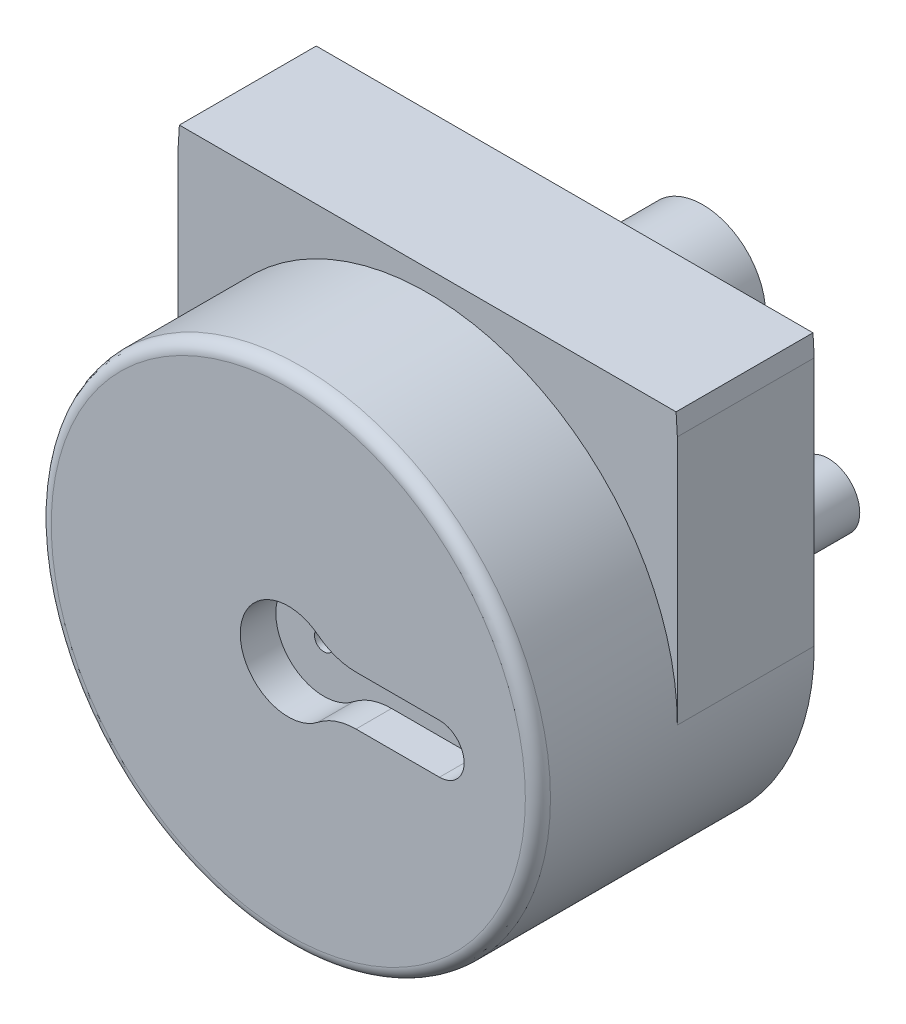
SolidWorks part; units mm, degrees
ref_plane "Front Plane" through (0, 0, 0) normal (0, 0, 1) x (1, 0, 0)
ref_plane "Top Plane" through (0, 0, 0) normal (0, 1, 0) x (1, 0, 0)
ref_plane "Right Plane" through (0, 0, 0) normal (1, 0, 0) x (0, 0, -1)
sketch "Sketch2" plane through (0, 0, 0) normal (0, 0, 1) x (1, 0, 0)
  circle A0 centre (0, 0) radius 39.75
  dimension "D1" = 79.5
extrude "Boss-Extrude1" add sketch "Sketch2" along normal blind 44
sketch "Sketch3" plane through (0, 0, 0) normal (0, 1, 0) x (1, 0, 0)
  line L0 (39.75, -44) -> (39.75, 0) construction
  line L1 (-39.75, 0) -> (39.75, 0)
  line L2 (-39.75, 0) -> (-39.75, -21.8)
  line L3 (-39.75, -21.8) -> (39.75, -21.8)
  line L4 (39.75, 0) -> (39.75, -21.8)
  dimension "D1" = 21.8
extrude "Boss-Extrude2" add sketch "Sketch3" along normal through all
sketch "Sketch4" plane through (0, 0, 0) normal (0, 0, -1) x (-1, 0, 0)
  line L0 (0, 0) -> (0, 203.2) construction
  line L1 (-39.75, 39.75) -> (-29.9473, 204.9767)
  line L2 (39.75, 39.75) -> (29.9473, 204.9767)
  line L3 (-39.75, 39.75) -> (39.75, 39.75)
  circle A0 centre (0, 203.2) radius 30
  circle A1 centre (0, 203.2) radius 25.9
  line M5 (39.75, 39.75) -> (-39.75, 39.75)
  dimension "D2" = 60
  dimension "D3" = 51.8
  dimension "D1" = 203.2
extrude "Boss-Extrude3" add sketch "Sketch4" against normal up to surface (21.8 mm away) contours L0 L2 A0 M5 | L3 L0 A0 L1 | A0 region at (18.2462, 107.3979, 0) region at (-18.2462, 107.3979, 0) region at (21.2148, 183.2065, 0) up to face at (29.2442, 29.2442, 21.8)
sketch "Sketch5" plane through (0, 0, 0) normal (0, 0, -1) x (-1, 0, 0)
  line L0 (-20, 0) -> (20, 0) construction
  line L1 (0, 20) -> (0, -20) construction
  line L2 (0, 0) -> (0, 177.3) construction
  circle A0 centre (-20, 0) radius 5
  circle A1 centre (0, -20) radius 10
  circle A2 centre (0, 20) radius 10
  circle A3 centre (20, 0) radius 5
  circle A4 centre (0, 203.2) radius 25.9 construction
  circle A5 centre (0, 147.3) radius 5
  circle A6 centre (0, 117.3) radius 10
  circle A7 centre (0, -20) radius 5.125
  circle A8 centre (0, 20) radius 5.125
  circle A9 centre (0, 117.3) radius 5.125
  point P5 (0, 0)
  point P9 (0, 0)
  dimension "D3" = 10
  dimension "D4" = 20
  dimension "D7" = 10
  dimension "D8" = 10
  dimension "D9" = 20
  dimension "D10" = 20
  dimension "D11" = 10.25
  dimension "D12" = 10.25
  dimension "D13" = 10.25
  dimension "D1" = 40
  dimension "D2" = 40
  dimension "D5" = 30
  dimension "D6" = 30
extrude "Boss-Extrude4" add sketch "Sketch5" along normal blind 22
extrude "Boss-Extrude5" add sketch "Sketch4<3>" along normal blind 10 from surface contours A1 region at (0, 203.2, 0) starting at face at (0, 92.9045, 21.8)
sketch "Sketch4<3>" plane through (0, 0, 0) normal (0, 0, -1) x (-1, 0, 0) same geometry as "Sketch4"
sketch "Sketch6" plane through (0, 0, 44) normal (0, 0, 1) x (1, 0, 0)
  line L0 (24.0717, 0) -> (20.0717, 0) construction
  line L1 (10.7762, 3.725) -> (24.0717, 3.725)
  line L2 (24.0717, -3) -> (20.0717, -3)
  line L7 (10.7762, -3.725) -> (24.0717, -3.725)
  line L8 (24.0717, 3) -> (20.0717, 3)
  line L9 (10.7762, -3.925) -> (24.0717, -3.925)
  line L10 (10.7762, 3.925) -> (24.0717, 3.925)
  arc A2 (24.0717, -3.725) -> (24.0717, 3.725) centre (24.0717, 0) ccw
  arc A3 (24.0717, -3) -> (24.0717, 3) centre (24.0717, 0) ccw
  arc A4 (6.4519, 3.725) -> (7.4142, 0.729) centre (0, 0) cw
  arc A5 (4.6007, -5.8597) -> (10.7762, -3.725) centre (10.7762, -13.725) cw
  arc A6 (4.6007, 5.8597) -> (10.7762, 3.725) centre (10.7762, 13.725) ccw
  arc A7 (4.7242, 6.017) -> (4.7242, -6.017) centre (0, 0) ccw
  arc A8 (4.7242, -6.017) -> (10.7762, -3.925) centre (10.7762, -13.725) cw
  arc A9 (24.0717, -3.925) -> (24.0717, 3.925) centre (24.0717, 0) ccw
  arc A10 (4.7242, 6.017) -> (10.7762, 3.925) centre (10.7762, 13.725) ccw
  circle A11 centre (0, 0) radius 1.5
  circle A12 centre (8.95, 0) radius 1.7
  circle A13 centre (20.0717, 0) radius 1.5
  circle A14 centre (24.0717, 0) radius 1.5
  arc A15 (7.4142, -0.729) -> (6.4519, -3.725) centre (0, 0) cw
  point P1 (22.0717, 0)
  point P4 (0, 0)
  point P5 (0, 0)
  point P8 (0, 0)
  point P10 (-27.75, 0)
  point P13 (27.75, 0)
  dimension "D4" = 10
  dimension "D1" = 7.45
  dimension "D5" = 3
  dimension "D6" = 3
  dimension "D7" = 3
  dimension "D2" = 24.0717
  dimension "D3" = 6
extrude "Cut-Extrude1(NEW)" cut sketch "Sketch6" against normal blind 5.67 contours A10 A7 A8 L9 A9 L10 A14 A13 A11 A12 region at (7.4478, -4.0961, 44)
fillet "Fillet1" radius 2 1 edges at (39.75, 0, 44)
sketch "Sketch7" plane through (41.9606, 2.4895, 0) normal (0.9982, 0.0592, 0) x (0, 0, -1)
  line L0 (-1.8, 184.6917) -> (-1.8, 181.1738)
  line L1 (-11.8422, 116.1491) -> (-16.6583, 116.1491)
  line L2 (-2, 184.4917) -> (-2, 181.1738)
  line L3 (-15.0457, 174.0211) -> (-19.8, 174.0211)
  line L4 (-19.8, 174.0211) -> (-19.8, 178.4187)
  line L5 (-19.8, 178.4187) -> (-13.7794, 178.4187)
  line L6 (-11.6329, 179.8846) -> (-19.8, 179.8846)
  line L7 (-19.8, 179.8846) -> (-19.8, 184.4917)
  line L8 (-19.8, 184.4917) -> (-2, 184.4917)
  line L9 (-4.9318, 179.8846) -> (-8.9106, 179.8846)
  line L10 (-7.2975, 178.4187) -> (-6.3126, 178.4187)
  line L11 (-2, 162.5453) -> (-2, 154.5877)
  line L12 (-2, 154.5877) -> (-5.56, 154.5877)
  line L13 (-5.56, 154.5877) -> (-5.56, 157.9383)
  line L14 (-5.56, 157.9383) -> (-8.9106, 157.9383)
  line L15 (-8.9106, 157.9383) -> (-8.9106, 154.7971)
  line L16 (-8.9106, 154.7971) -> (-12.2612, 154.7971)
  line L17 (-12.2612, 154.7971) -> (-12.2612, 157.9383)
  line L18 (-12.2612, 157.9383) -> (-16.24, 157.9383)
  line L19 (-16.24, 157.9383) -> (-16.24, 154.3783)
  line L20 (-16.24, 154.3783) -> (-19.8, 154.3783)
  line L21 (-19.8, 154.3783) -> (-19.8, 162.5453)
  line L22 (-19.8, 162.5453) -> (-2, 162.5453)
  line L23 (-2, 143.3213) -> (-2, 139.8038)
  line L24 (-8.2791, 132.4319) -> (-14.5124, 132.4319)
  line L25 (-19.8, 137.3923) -> (-19.8, 143.3213)
  line L26 (-19.8, 143.3213) -> (-2, 143.3213)
  line L27 (-4.9318, 138.7143) -> (-16.8682, 138.7143)
  line L28 (-14.2342, 137.039) -> (-7.1829, 137.039)
  line L29 (-2, 120.9561) -> (-2, 116.2346)
  line L30 (-13.8939, 110.0667) -> (-15.566, 110.0667)
  line L31 (-19.8, 115.5441) -> (-19.8, 120.9561)
  line L32 (-19.8, 120.9561) -> (-2, 120.9561)
  line L33 (-4.9318, 116.3491) -> (-8.9106, 116.3491)
  line L34 (-11.6329, 116.3491) -> (-16.8682, 116.3491)
  line L35 (-15.1242, 114.6738) -> (-13.3769, 114.6738)
  line L36 (-2, 93.9839) -> (-19.8, 93.9839)
  line L37 (-19.8, 93.9839) -> (-19.8, 98.591)
  line L38 (-19.8, 98.591) -> (-2, 98.591)
  line L39 (-2, 98.591) -> (-2, 93.9839)
  line L40 (-2, 82.2987) -> (-2, 78.9809)
  line L41 (-15.0457, 71.8281) -> (-19.8, 71.8281)
  line L42 (-19.8, 71.8281) -> (-19.8, 76.2258)
  line L43 (-19.8, 76.2258) -> (-13.7794, 76.2258)
  line L44 (-11.6329, 77.6917) -> (-19.8, 77.6917)
  line L45 (-19.8, 77.6917) -> (-19.8, 82.2987)
  line L46 (-19.8, 82.2987) -> (-2, 82.2987)
  line L47 (-4.9318, 77.6917) -> (-8.9106, 77.6917)
  line L48 (-7.2975, 76.2258) -> (-6.3126, 76.2258)
  line L49 (-2, 60.3524) -> (-2, 56.8349)
  line L50 (-8.2791, 49.463) -> (-14.5124, 49.463)
  line L51 (-19.8, 54.4234) -> (-19.8, 60.3524)
  line L52 (-19.8, 60.3524) -> (-2, 60.3524)
  line L53 (-4.9318, 55.7453) -> (-16.8682, 55.7453)
  line L54 (-14.2342, 54.07) -> (-7.1829, 54.07)
  line L55 (-15.0442, 173.8211) -> (-20, 173.8211)
  line L56 (-20, 173.8211) -> (-20, 178.6187)
  line L57 (-20, 178.6187) -> (-13.7794, 178.6187)
  line L58 (-11.8379, 179.6846) -> (-20, 179.6846)
  line L59 (-20, 179.6846) -> (-20, 184.6917)
  line L60 (-20, 184.6917) -> (-1.8, 184.6917)
  line L61 (-7.2947, 178.6187) -> (-6.3136, 178.6187)
  line L62 (-5.1372, 179.6846) -> (-8.7079, 179.6846)
  line L63 (-20, 162.7453) -> (-1.8, 162.7453)
  line L64 (-1.8, 162.7453) -> (-1.8, 154.3877)
  line L65 (-1.8, 154.3877) -> (-5.76, 154.3877)
  line L66 (-5.76, 154.3877) -> (-5.76, 157.7383)
  line L67 (-5.76, 157.7383) -> (-8.7106, 157.7383)
  line L68 (-8.7106, 157.7383) -> (-8.7106, 154.5971)
  line L69 (-8.7106, 154.5971) -> (-12.4612, 154.5971)
  line L70 (-12.4612, 154.5971) -> (-12.4612, 157.7383)
  line L71 (-12.4612, 157.7383) -> (-16.04, 157.7383)
  line L72 (-16.04, 157.7383) -> (-16.04, 154.1783)
  line L73 (-16.04, 154.1783) -> (-20, 154.1783)
  line L74 (-20, 154.1783) -> (-20, 162.7453)
  line L75 (-20, 143.5213) -> (-1.8, 143.5213)
  line L76 (-1.8, 143.5213) -> (-1.8, 139.8038)
  line L77 (-8.2784, 132.2319) -> (-14.5128, 132.2319)
  line L78 (-20, 137.3909) -> (-20, 143.5213)
  line L79 (-15.1267, 114.8738) -> (-13.3758, 114.8738)
  line L80 (-5.1361, 116.1491) -> (-8.7058, 116.1491)
  line L81 (-20, 98.791) -> (-1.8, 98.791)
  line L82 (-1.8, 98.791) -> (-1.8, 93.7839)
  line L83 (-5.1349, 138.5143) -> (-16.6645, 138.5143)
  line L84 (-14.2351, 137.239) -> (-7.1805, 137.239)
  line L85 (-20, 121.1561) -> (-1.8, 121.1561)
  line L86 (-1.8, 121.1561) -> (-1.8, 116.2334)
  line L87 (-13.8936, 109.8667) -> (-15.566, 109.8667)
  line L88 (-20, 115.5431) -> (-20, 121.1561)
  line L89 (-1.8, 93.7839) -> (-20, 93.7839)
  line L90 (-20, 93.7839) -> (-20, 98.791)
  line L91 (-20, 82.4987) -> (-1.8, 82.4987)
  line L92 (-1.8, 82.4987) -> (-1.8, 78.9809)
  line L93 (-15.0442, 71.6281) -> (-20, 71.6281)
  line L94 (-20, 71.6281) -> (-20, 76.4258)
  line L95 (-20, 76.4258) -> (-13.7794, 76.4258)
  line L96 (-11.8379, 77.4917) -> (-20, 77.4917)
  line L97 (-20, 77.4917) -> (-20, 82.4987)
  line L98 (-7.2947, 76.4258) -> (-6.3136, 76.4258)
  line L99 (-5.1372, 77.4917) -> (-8.7079, 77.4917)
  line L100 (-14.2351, 54.27) -> (-7.1805, 54.27)
  line L101 (-5.1349, 55.5453) -> (-16.6645, 55.5453)
  line L102 (-20, 54.4219) -> (-20, 60.5524)
  line L103 (-20, 60.5524) -> (-1.8, 60.5524)
  line L104 (-1.8, 60.5524) -> (-1.8, 56.8349)
  line L105 (-8.2784, 49.263) -> (-14.5128, 49.263)
  spline S0 degree 3 poles (-2, 181.1738) (-1.9981, 180.6655) (-2.0068, 179.9357) (-2.034, 179.0075) (-2.0583, 178.4118) (-2.0946, 177.8838) (-2.1365, 177.4223) (-2.1832, 177.0267) (-2.2422, 176.6885) (-2.3184, 176.3914) (-2.4187, 176.1172) (-2.5379, 175.8548) (-2.6869, 175.6074) (-2.8617, 175.3763) (-3.0552, 175.1541) (-3.2763, 174.948) (-3.5217, 174.7536) (-3.7998, 174.5772) (-4.1159, 174.4286) (-4.4681, 174.2996) (-4.8602, 174.2012) (-5.2883, 174.1194) (-5.9348, 174.0377) (-6.4412, 174.0257) (-6.7903, 174.0211) knots 0 0 0 0 0.148543 0.213274 0.27134 0.322776 0.367908 0.406771 0.439156 0.468147 0.496277 0.524371 0.552249 0.580489 0.608944 0.638258 0.668673 0.700331 0.734261 0.77056 0.809755 0.852263 0.897886 1 1 1 1
  spline S1 degree 3 poles (-6.7903, 174.0211) (-7.1039, 174.0159) (-7.5537, 174.0372) (-8.1248, 174.0861) (-8.4902, 174.1472) (-8.8148, 174.2161) (-9.0987, 174.3045) (-9.3418, 174.4065) (-9.5475, 174.5307) (-9.7181, 174.6841) (-9.8698, 174.8618) (-10.0023, 175.0725) (-10.1145, 175.3152) (-10.2133, 175.5875) (-10.3205, 176.0108) (-10.3706, 176.3476) (-10.3896, 176.5831) knots 0 0 0 0 0.183754 0.264085 0.33602 0.400896 0.458558 0.510133 0.555226 0.598736 0.644114 0.691853 0.744219 0.800677 0.861499 1 1 1 1
  spline S2 degree 3 poles (-10.3896, 176.5831) (-10.4477, 176.3705) (-10.53, 176.0622) (-10.6742, 175.6791) (-10.7897, 175.4345) (-10.9067, 175.215) (-11.0338, 175.0254) (-11.1684, 174.8627) (-11.3529, 174.6892) (-11.5852, 174.5151) (-11.8564, 174.3409) (-12.1197, 174.2167) (-12.3412, 174.1385) (-12.543, 174.1055) (-12.7439, 174.0834) (-12.9983, 174.0648) (-13.3059, 174.0488) (-13.6659, 174.0363) (-14.2516, 174.0213) (-14.7174, 174.0259) (-15.0457, 174.0211) knots 0 0 0 0 0.110219 0.159211 0.20432 0.245296 0.283389 0.318211 0.350594 0.409678 0.463061 0.511332 0.554938 0.579849 0.613314 0.655951 0.707257 0.767249 0.835943 1 1 1 1
  spline S3 degree 3 poles (-13.7794, 178.4187) (-13.5603, 178.4206) (-13.2487, 178.4204) (-12.8563, 178.4494) (-12.6138, 178.474) (-12.4051, 178.5065) (-12.2319, 178.5444) (-12.0913, 178.5887) (-11.9798, 178.6452) (-11.8926, 178.722) (-11.8245, 178.8214) (-11.7614, 178.9389) (-11.7129, 179.0826) (-11.6789, 179.2498) (-11.6423, 179.519) (-11.6342, 179.7339) (-11.6329, 179.8846) knots 0 0 0 0 0.208642 0.296034 0.374307 0.440504 0.496897 0.54284 0.580443 0.615002 0.652158 0.694401 0.741661 0.795804 0.856563 1 1 1 1
  spline S4 degree 3 poles (-8.9106, 179.8846) (-8.9127, 179.6528) (-8.8925, 179.3307) (-8.8017, 178.9494) (-8.7231, 178.769) (-8.6251, 178.6601) (-8.5222, 178.5947) (-8.3901, 178.5409) (-8.2286, 178.4959) (-8.038, 178.4611) (-7.7252, 178.4234) (-7.474, 178.4237) (-7.2975, 178.4187) knots 0 0 0 0 0.263059 0.362536 0.443753 0.482229 0.526771 0.580464 0.643421 0.71635 0.799709 1 1 1 1
  spline S5 degree 3 poles (-6.3126, 178.4187) (-6.0777, 178.4211) (-5.7485, 178.4373) (-5.374, 178.5775) (-5.1844, 178.7238) (-5.0685, 178.9346) (-4.9447, 179.3168) (-4.9363, 179.6497) (-4.9318, 179.8846) knots 0 0 0 0 0.296724 0.405999 0.497474 0.590179 0.702697 1 1 1 1
  spline S6 degree 3 poles (-2, 139.8038) (-1.9956, 139.2824) (-2.0094, 138.534) (-2.0395, 137.583) (-2.0704, 136.9718) (-2.117, 136.4308) (-2.1678, 135.957) (-2.2277, 135.5525) (-2.3206, 135.1143) (-2.4728, 134.6455) (-2.6938, 134.1448) (-2.9758, 133.7187) (-3.306, 133.3657) (-3.6705, 133.0823) (-4.0556, 132.8554) (-4.4605, 132.687) (-4.8224, 132.5944) (-5.145, 132.5497) (-5.4395, 132.5163) (-5.7856, 132.4926) (-6.1836, 132.4682) (-6.6332, 132.4541) (-7.3377, 132.4339) (-7.8919, 132.4347) (-8.2791, 132.4319) knots 0 0 0 0 0.131289 0.188445 0.2396 0.285351 0.325141 0.359593 0.388249 0.437842 0.483436 0.525634 0.565855 0.604586 0.641514 0.678082 0.71465 0.735196 0.760065 0.789259 0.822545 0.860469 0.902502 1 1 1 1
  spline S7 degree 3 poles (-14.5124, 132.4319) (-14.8788, 132.4334) (-15.4037, 132.4345) (-16.0701, 132.4621) (-16.4954, 132.4892) (-16.8711, 132.5159) (-17.1978, 132.5544) (-17.4737, 132.6035) (-17.7737, 132.6699) (-18.0937, 132.7877) (-18.4383, 132.9635) (-18.7347, 133.1895) (-18.9908, 133.4536) (-19.2002, 133.7606) (-19.376, 134.0986) (-19.5222, 134.4686) (-19.6098, 134.8037) (-19.666, 135.0966) (-19.7004, 135.3469) (-19.7347, 135.6226) (-19.7552, 135.9263) (-19.7747, 136.2546) (-19.7999, 136.7463) (-19.7961, 137.1285) (-19.8, 137.3923) knots 0 0 0 0 0.124488 0.178251 0.226503 0.269237 0.306181 0.338157 0.364398 0.41045 0.453534 0.495323 0.536458 0.577977 0.621061 0.66564 0.712819 0.738467 0.766915 0.798622 0.832803 0.870286 0.91034 1 1 1 1
  spline S8 degree 3 poles (-16.8682, 138.7143) (-16.8674, 138.5419) (-16.8597, 138.2945) (-16.8125, 137.9868) (-16.774, 137.7943) (-16.7118, 137.6326) (-16.647, 137.4922) (-16.5606, 137.3829) (-16.4579, 137.2963) (-16.325, 137.2337) (-16.1549, 137.1834) (-15.9413, 137.1388) (-15.6846, 137.1004) (-15.3843, 137.0715) (-14.8966, 137.0461) (-14.5081, 137.0366) (-14.2342, 137.039) knots 0 0 0 0 0.137111 0.195798 0.247293 0.292517 0.333199 0.369595 0.402207 0.439014 0.485321 0.542924 0.61215 0.691372 0.782487 1 1 1 1
  spline S9 degree 3 poles (-7.1829, 137.039) (-6.9964, 137.0344) (-6.7303, 137.0433) (-6.3932, 137.051) (-6.1815, 137.06) (-5.9985, 137.0747) (-5.8429, 137.0846) (-5.7157, 137.1062) (-5.582, 137.1289) (-5.443, 137.1804) (-5.2977, 137.2649) (-5.1805, 137.3845) (-5.0837, 137.5372) (-5.0121, 137.741) (-4.9386, 138.1366) (-4.9349, 138.4712) (-4.9318, 138.7143) knots 0 0 0 0 0.161879 0.231001 0.29259 0.34573 0.390378 0.427726 0.457613 0.507913 0.555475 0.602325 0.65169 0.711291 0.788512 1 1 1 1
  spline S10 degree 3 poles (-2, 116.2346) (-2.004, 115.8844) (-2.0071, 115.3757) (-2.042, 114.7201) (-2.0831, 114.2796) (-2.1261, 113.872) (-2.1857, 113.4989) (-2.2533, 113.1591) (-2.3315, 112.8491) (-2.428, 112.5637) (-2.5413, 112.2943) (-2.6802, 112.0405) (-2.8415, 111.8018) (-3.0217, 111.574) (-3.2259, 111.3622) (-3.4483, 111.1608) (-3.6966, 110.9765) (-3.9726, 110.805) (-4.2921, 110.6683) (-4.6448, 110.5411) (-5.0405, 110.4471) (-5.4714, 110.3665) (-6.1256, 110.2999) (-6.6357, 110.27) (-6.9899, 110.2761) knots 0 0 0 0 0.114386 0.166124 0.214411 0.258869 0.299987 0.337788 0.372007 0.404341 0.436105 0.467354 0.498678 0.530114 0.562118 0.594663 0.628011 0.663022 0.700498 0.741288 0.785356 0.833155 0.88442 1 1 1 1
  spline S11 degree 3 poles (-6.9899, 110.2761) (-7.227, 110.2723) (-7.5686, 110.2901) (-8.0022, 110.3443) (-8.2864, 110.3943) (-8.5399, 110.4664) (-8.7663, 110.5513) (-8.964, 110.6518) (-9.1363, 110.7725) (-9.2872, 110.9181) (-9.4253, 111.0915) (-9.5554, 111.2929) (-9.6721, 111.5272) (-9.7889, 111.7874) (-9.924, 112.1979) (-10.0157, 112.5216) (-10.0624, 112.7498) knots 0 0 0 0 0.159593 0.229912 0.29415 0.353664 0.407126 0.456721 0.502563 0.548271 0.597357 0.65154 0.709345 0.77347 0.843372 1 1 1 1
  spline S12 degree 3 poles (-10.0624, 112.7498) (-10.1183, 112.5059) (-10.2185, 112.155) (-10.399, 111.7216) (-10.5418, 111.4376) (-10.7034, 111.1867) (-10.8795, 110.9669) (-11.0712, 110.7773) (-11.2803, 110.6181) (-11.5114, 110.4844) (-11.7699, 110.3755) (-12.0528, 110.2751) (-12.3685, 110.2033) (-12.7087, 110.1399) (-13.2206, 110.0833) (-13.6187, 110.0677) (-13.8939, 110.0667) knots 0 0 0 0 0.14404 0.209305 0.269928 0.326675 0.380677 0.43171 0.481413 0.531464 0.584861 0.642612 0.703952 0.770914 0.841672 1 1 1 1
  spline S13 degree 3 poles (-15.566, 110.0667) (-15.8508, 110.0669) (-16.2639, 110.0774) (-16.7938, 110.1221) (-17.1478, 110.1668) (-17.4717, 110.2267) (-17.768, 110.2926) (-18.0337, 110.3781) (-18.3432, 110.5062) (-18.6861, 110.7034) (-19.0241, 111.0158) (-19.3008, 111.3821) (-19.4658, 111.7453) (-19.5628, 112.086) (-19.6261, 112.4046) (-19.682, 112.7823) (-19.7208, 113.2195) (-19.7579, 113.7157) (-19.7943, 114.4967) (-19.7954, 115.1134) (-19.8, 115.5441) knots 0 0 0 0 0.102225 0.148189 0.190817 0.230204 0.266378 0.299678 0.330209 0.386533 0.440563 0.494267 0.550311 0.582518 0.621285 0.666789 0.719486 0.778749 0.845365 1 1 1 1
  spline S14 degree 2 poles (-8.9106, 116.3491) (-8.9038, 116.0939) (-8.9008, 115.8386) knots 0 0 0 1 1 1
  spline S15 degree 3 poles (-8.9008, 115.8386) (-8.9036, 115.6319) (-8.8787, 115.3414) (-8.7282, 115.0182) (-8.5926, 114.8871) (-8.4492, 114.824) (-8.3051, 114.7827) (-8.1215, 114.7526) (-7.9002, 114.7227) (-7.638, 114.701) (-7.2116, 114.6784) (-6.8721, 114.6739) (-6.6332, 114.6738) knots 0 0 0 0 0.207123 0.283932 0.350841 0.389257 0.439129 0.499893 0.574453 0.661745 0.761896 1 1 1 1
  spline S16 degree 3 poles (-6.6332, 114.6738) (-6.3937, 114.6721) (-6.0649, 114.6867) (-5.6703, 114.757) (-5.4631, 114.8337) (-5.3036, 114.9277) (-5.1808, 115.0341) (-5.0833, 115.1501) (-5.0215, 115.2942) (-4.9847, 115.475) (-4.9423, 115.8295) (-4.9357, 116.1287) (-4.9318, 116.3491) knots 0 0 0 0 0.247841 0.339943 0.41354 0.475302 0.530527 0.581127 0.630646 0.690893 0.771688 1 1 1 1
  spline S17 degree 3 poles (-16.8682, 116.3491) (-16.8607, 116.1854) (-16.8509, 115.9506) (-16.8087, 115.6568) (-16.7744, 115.4715) (-16.7282, 115.3109) (-16.6771, 115.1734) (-16.6194, 115.0592) (-16.5473, 114.9684) (-16.4559, 114.897) (-16.3441, 114.8341) (-16.2026, 114.7873) (-16.0376, 114.7452) (-15.846, 114.7129) (-15.5394, 114.6828) (-15.2958, 114.6696) (-15.1242, 114.6738) knots 0 0 0 0 0.168587 0.241054 0.305045 0.362185 0.41258 0.455716 0.49319 0.530665 0.574337 0.624343 0.683356 0.749349 0.823768 1 1 1 1
  spline S18 degree 3 poles (-13.3769, 114.6738) (-13.1968, 114.6716) (-12.9412, 114.6806) (-12.6194, 114.7069) (-12.4221, 114.7341) (-12.2551, 114.7745) (-12.1175, 114.8188) (-12.0065, 114.8697) (-11.9197, 114.9351) (-11.8601, 115.0258) (-11.8035, 115.1333) (-11.7595, 115.2708) (-11.721, 115.4339) (-11.689, 115.6242) (-11.6524, 115.9315) (-11.6392, 116.1765) (-11.6329, 116.3491) knots 0 0 0 0 0.182369 0.25887 0.326977 0.383772 0.432672 0.473181 0.506991 0.541018 0.58202 0.629874 0.686669 0.751678 0.825111 1 1 1 1
  spline S19 degree 3 poles (-2, 78.9809) (-1.9981, 78.4725) (-2.0068, 77.7427) (-2.034, 76.8146) (-2.0583, 76.2188) (-2.0946, 75.6909) (-2.1365, 75.2293) (-2.1832, 74.8337) (-2.2422, 74.4956) (-2.3184, 74.1985) (-2.4187, 73.9243) (-2.5379, 73.6619) (-2.6869, 73.4144) (-2.8617, 73.1834) (-3.0552, 72.9611) (-3.2763, 72.7551) (-3.5217, 72.5607) (-3.7998, 72.3842) (-4.1159, 72.2357) (-4.4681, 72.1066) (-4.8602, 72.0083) (-5.2883, 71.9265) (-5.9348, 71.8448) (-6.4412, 71.8328) (-6.7903, 71.8281) knots 0 0 0 0 0.148543 0.213274 0.27134 0.322776 0.367908 0.406771 0.439156 0.468147 0.496277 0.524371 0.552249 0.580489 0.608944 0.638258 0.668673 0.700331 0.734261 0.77056 0.809755 0.852263 0.897886 1 1 1 1
  spline S20 degree 3 poles (-6.7903, 71.8281) (-7.1039, 71.8229) (-7.5537, 71.8442) (-8.1248, 71.8931) (-8.4902, 71.9543) (-8.8148, 72.0232) (-9.0987, 72.1116) (-9.3418, 72.2136) (-9.5475, 72.3378) (-9.7181, 72.4912) (-9.8698, 72.6688) (-10.0023, 72.8796) (-10.1145, 73.1223) (-10.2133, 73.3946) (-10.3205, 73.8178) (-10.3706, 74.1547) (-10.3896, 74.3902) knots 0 0 0 0 0.183754 0.264085 0.33602 0.400896 0.458558 0.510133 0.555226 0.598736 0.644114 0.691853 0.744219 0.800677 0.861499 1 1 1 1
  spline S21 degree 3 poles (-10.3896, 74.3902) (-10.4477, 74.1775) (-10.53, 73.8692) (-10.6742, 73.4862) (-10.7897, 73.2416) (-10.9067, 73.0221) (-11.0338, 72.8325) (-11.1684, 72.6697) (-11.3529, 72.4963) (-11.5852, 72.3221) (-11.8564, 72.1479) (-12.1197, 72.0237) (-12.3412, 71.9456) (-12.543, 71.9126) (-12.7439, 71.8905) (-12.9983, 71.8719) (-13.3059, 71.8559) (-13.6659, 71.8434) (-14.2516, 71.8283) (-14.7174, 71.8329) (-15.0457, 71.8281) knots 0 0 0 0 0.110219 0.159211 0.20432 0.245296 0.283389 0.318211 0.350594 0.409678 0.463061 0.511332 0.554938 0.579849 0.613314 0.655951 0.707257 0.767249 0.835943 1 1 1 1
  spline S22 degree 3 poles (-13.7794, 76.2258) (-13.5603, 76.2277) (-13.2487, 76.2274) (-12.8563, 76.2565) (-12.6138, 76.281) (-12.4051, 76.3136) (-12.2319, 76.3515) (-12.0913, 76.3957) (-11.9798, 76.4522) (-11.8926, 76.5291) (-11.8245, 76.6284) (-11.7614, 76.746) (-11.7129, 76.8897) (-11.6789, 77.0569) (-11.6423, 77.3261) (-11.6342, 77.541) (-11.6329, 77.6917) knots 0 0 0 0 0.208642 0.296034 0.374307 0.440504 0.496897 0.54284 0.580443 0.615002 0.652158 0.694401 0.741661 0.795804 0.856563 1 1 1 1
  spline S23 degree 3 poles (-8.9106, 77.6917) (-8.9127, 77.4599) (-8.8925, 77.1377) (-8.8017, 76.7565) (-8.7231, 76.5761) (-8.6251, 76.4671) (-8.5222, 76.4017) (-8.3901, 76.3479) (-8.2286, 76.3029) (-8.038, 76.2681) (-7.7252, 76.2304) (-7.474, 76.2307) (-7.2975, 76.2258) knots 0 0 0 0 0.263059 0.362536 0.443753 0.482229 0.526771 0.580464 0.643421 0.71635 0.799709 1 1 1 1
  spline S24 degree 3 poles (-6.3126, 76.2258) (-6.0777, 76.2281) (-5.7485, 76.2444) (-5.374, 76.3846) (-5.1844, 76.5309) (-5.0685, 76.7416) (-4.9447, 77.1238) (-4.9363, 77.4568) (-4.9318, 77.6917) knots 0 0 0 0 0.296724 0.405999 0.497474 0.590179 0.702697 1 1 1 1
  spline S25 degree 3 poles (-2, 56.8349) (-1.9956, 56.3134) (-2.0094, 55.5651) (-2.0395, 54.614) (-2.0704, 54.0028) (-2.117, 53.4619) (-2.1678, 52.988) (-2.2277, 52.5836) (-2.3206, 52.1454) (-2.4728, 51.6765) (-2.6938, 51.1759) (-2.9758, 50.7498) (-3.306, 50.3968) (-3.6705, 50.1134) (-4.0556, 49.8865) (-4.4605, 49.7181) (-4.8224, 49.6255) (-5.145, 49.5808) (-5.4395, 49.5474) (-5.7856, 49.5236) (-6.1836, 49.4993) (-6.6332, 49.4852) (-7.3377, 49.4649) (-7.8919, 49.4658) (-8.2791, 49.463) knots 0 0 0 0 0.131289 0.188445 0.2396 0.285351 0.325141 0.359593 0.388249 0.437842 0.483436 0.525634 0.565855 0.604586 0.641514 0.678082 0.71465 0.735196 0.760065 0.789259 0.822545 0.860469 0.902502 1 1 1 1
  spline S26 degree 3 poles (-14.5124, 49.463) (-14.8788, 49.4645) (-15.4037, 49.4656) (-16.0701, 49.4931) (-16.4954, 49.5203) (-16.8711, 49.547) (-17.1978, 49.5855) (-17.4737, 49.6346) (-17.7737, 49.701) (-18.0937, 49.8187) (-18.4383, 49.9945) (-18.7347, 50.2205) (-18.9908, 50.4847) (-19.2002, 50.7917) (-19.376, 51.1296) (-19.5222, 51.4997) (-19.6098, 51.8348) (-19.666, 52.1277) (-19.7004, 52.378) (-19.7347, 52.6537) (-19.7552, 52.9574) (-19.7747, 53.2857) (-19.7999, 53.7774) (-19.7961, 54.1595) (-19.8, 54.4234) knots 0 0 0 0 0.124488 0.178251 0.226503 0.269237 0.306181 0.338157 0.364398 0.41045 0.453534 0.495323 0.536458 0.577977 0.621061 0.66564 0.712819 0.738467 0.766915 0.798622 0.832803 0.870286 0.91034 1 1 1 1
  spline S27 degree 3 poles (-16.8682, 55.7453) (-16.8674, 55.573) (-16.8597, 55.3256) (-16.8125, 55.0179) (-16.774, 54.8254) (-16.7118, 54.6636) (-16.647, 54.5232) (-16.5606, 54.4139) (-16.4579, 54.3274) (-16.325, 54.2647) (-16.1549, 54.2144) (-15.9413, 54.1699) (-15.6846, 54.1315) (-15.3843, 54.1025) (-14.8966, 54.0772) (-14.5081, 54.0677) (-14.2342, 54.07) knots 0 0 0 0 0.137111 0.195798 0.247293 0.292517 0.333199 0.369595 0.402207 0.439014 0.485321 0.542924 0.61215 0.691372 0.782487 1 1 1 1
  spline S28 degree 3 poles (-7.1829, 54.07) (-6.9964, 54.0655) (-6.7303, 54.0744) (-6.3932, 54.0821) (-6.1815, 54.0911) (-5.9985, 54.1058) (-5.8429, 54.1156) (-5.7157, 54.1373) (-5.582, 54.1599) (-5.443, 54.2115) (-5.2977, 54.296) (-5.1805, 54.4156) (-5.0837, 54.5683) (-5.0121, 54.7721) (-4.9386, 55.1676) (-4.9349, 55.5022) (-4.9318, 55.7453) knots 0 0 0 0 0.161879 0.231001 0.29259 0.34573 0.390378 0.427726 0.457613 0.507913 0.555475 0.602325 0.65169 0.711291 0.788512 1 1 1 1
  spline S29 degree 1 poles (-1.8, 181.1738) (-6.7873, 173.8211) knots 0 0 1 1 construction
  spline S30 degree 1 poles (-6.7873, 173.8211) (-10.4498, 175.7107) knots 0 0 1 1 construction
  spline S31 degree 1 poles (-10.4498, 175.7107) (-15.0442, 173.8211) knots 0 0 1 1 construction
  spline S32 degree 1 poles (-13.7794, 178.6187) (-11.8379, 179.6846) knots 0 0 1 1 construction
  spline S33 degree 3 poles (-1.8, 181.1738) (-1.7968, 180.3152) (-1.8179, 179.0237) (-1.9251, 177.3173) (-2.1534, 175.9722) (-2.9767, 174.8255) (-4.1703, 174.1131) (-5.4878, 173.8607) (-6.3523, 173.8269) (-6.7873, 173.8211) knots 0.000072 0.000072 0.000072 0.000072 0.250046 0.375033 0.50002 0.625007 0.749994 0.874981 0.999968 0.999968 0.999968 0.999968
  spline S34 degree 3 poles (-6.7873, 173.8211) (-7.1505, 173.8151) (-7.8758, 173.846) (-8.7843, 173.9782) (-9.5172, 174.2381) (-9.9972, 174.6501) (-10.2858, 175.1709) (-10.4037, 175.5272) (-10.4498, 175.7107) knots 0.000063 0.000063 0.000063 0.000063 0.209226 0.418389 0.52297 0.627551 0.732133 0.836714 0.836714 0.836714 0.836714
  spline S35 degree 3 poles (-10.4498, 175.7107) (-10.5319, 175.4992) (-10.7143, 175.0904) (-11.1891, 174.5283) (-11.6619, 174.2161) (-12.074, 174.0121) (-12.5607, 173.8771) (-13.0976, 173.8618) (-13.9687, 173.8193) (-14.6128, 173.8274) (-15.0442, 173.8211) knots 0.139503 0.139503 0.139503 0.139503 0.247096 0.354688 0.462281 0.516077 0.569873 0.677466 0.785059 1.000244 1.000244 1.000244 1.000244
  spline S36 degree 3 poles (-13.7794, 178.6187) (-13.5379, 178.6208) (-13.1732, 178.6225) (-12.6975, 178.6636) (-12.3477, 178.7163) (-12.0997, 178.791) (-12.0153, 178.8911) (-11.9139, 179.0732) (-11.8651, 179.3308) (-11.8429, 179.569) (-11.8379, 179.6846) knots 0.000547 0.000547 0.000547 0.000547 0.233854 0.350508 0.467161 0.583815 0.642142 0.700469 0.817122 0.933776 0.933776 0.933776 0.933776
  spline S37 degree 1 poles (-8.7079, 179.6846) (-7.2947, 178.6187) knots 0 0 1 1 construction
  spline S38 degree 1 poles (-6.3136, 178.6187) (-5.1372, 179.6846) knots 0 0 1 1 construction
  spline S39 degree 3 poles (-8.7079, 179.6846) (-8.7006, 179.4953) (-8.6697, 179.2014) (-8.5564, 178.8616) (-8.4393, 178.7665) (-8.1681, 178.6829) (-7.7971, 178.6266) (-7.4922, 178.6242) (-7.2947, 178.6187) knots 0.078446 0.078446 0.078446 0.078446 0.308574 0.423638 0.538703 0.653767 0.768831 0.99896 0.99896 0.99896 0.99896
  spline S40 degree 3 poles (-6.3136, 178.6187) (-6.1432, 178.6205) (-5.7914, 178.6357) (-5.4146, 178.7636) (-5.2786, 178.954) (-5.1659, 179.2615) (-5.1439, 179.5177) (-5.1372, 179.6846) knots 0.000432 0.000432 0.000432 0.000432 0.228515 0.456599 0.57064 0.684682 0.912765 0.912765 0.912765 0.912765
  spline S41 degree 1 poles (-1.8, 139.8038) (-8.2784, 132.2319) knots 0 0 1 1 construction
  spline S42 degree 1 poles (-14.5128, 132.2319) (-20, 137.3909) knots 0 0 1 1 construction
  spline S43 degree 3 poles (-1.8, 139.8038) (-1.7958, 139.3051) (-1.8118, 138.3079) (-1.8712, 136.8114) (-2.0132, 135.3082) (-2.5341, 133.7958) (-3.5287, 132.8634) (-4.5086, 132.4366) (-5.546, 132.286) (-6.7833, 132.2431) (-7.7806, 132.2355) (-8.2784, 132.2319) knots 0.000141 0.000141 0.000141 0.000141 0.125131 0.250121 0.375111 0.500101 0.625091 0.687586 0.750081 0.875071 1.000061 1.000061 1.000061 1.000061
  spline S44 degree 3 poles (-14.5128, 132.2319) (-14.8826, 132.2334) (-15.6234, 132.2359) (-16.7267, 132.2954) (-17.875, 132.4199) (-18.9689, 133.0053) (-19.6287, 134.03) (-20.0023, 135.5434) (-19.9889, 136.6467) (-20, 137.3909) knots -0.000046 -0.000046 -0.000046 -0.000046 0.12498 0.250007 0.375034 0.500061 0.625088 0.750115 1.000168 1.000168 1.000168 1.000168
  spline S45 degree 1 poles (-16.6645, 138.5143) (-14.2351, 137.239) knots 0 0 1 1 construction
  spline S46 degree 1 poles (-7.1805, 137.239) (-5.1349, 138.5143) knots 0 0 1 1 construction
  spline S47 degree 3 poles (-16.6645, 138.5143) (-16.6549, 138.2425) (-16.5903, 137.7684) (-16.3746, 137.4361) (-15.979, 137.3463) (-15.5519, 137.2829) (-14.9722, 137.2479) (-14.5288, 137.2365) (-14.2351, 137.239) knots 0.054835 0.054835 0.054835 0.054835 0.291183 0.409356 0.52753 0.645704 0.763877 1.000225 1.000225 1.000225 1.000225
  spline S48 degree 3 poles (-7.1805, 137.239) (-6.9133, 137.2324) (-6.5145, 137.2433) (-5.9743, 137.274) (-5.4777, 137.321) (-5.1641, 137.691) (-5.1404, 138.2611) (-5.1349, 138.5143) knots -0.000707 -0.000707 -0.000707 -0.000707 0.234678 0.35237 0.470063 0.705448 0.940832 0.940832 0.940832 0.940832
  spline S49 degree 1 poles (-1.8, 116.2334) (-6.99, 110.0761) knots 0 0 1 1 construction
  spline S50 degree 1 poles (-6.99, 110.0761) (-10.0704, 112.0069) knots 0 0 1 1 construction
  spline S51 degree 1 poles (-10.0704, 112.0069) (-13.8936, 109.8667) knots 0 0 1 1 construction
  spline S52 degree 1 poles (-15.566, 109.8667) (-20, 115.5431) knots 0 0 1 1 construction
  spline S53 degree 3 poles (-1.8, 116.2334) (-1.8088, 115.4614) (-1.8401, 114.3118) (-2.0956, 112.7541) (-2.6313, 111.6344) (-3.5131, 110.774) (-4.6533, 110.2833) (-5.822, 110.1138) (-6.6002, 110.0695) (-6.99, 110.0761) knots -0.000124 -0.000124 -0.000124 -0.000124 0.249818 0.37479 0.499761 0.624733 0.749704 0.874675 0.999647 0.999647 0.999647 0.999647
  spline S54 degree 3 poles (-6.99, 110.0761) (-7.312, 110.0711) (-7.9517, 110.1166) (-8.7632, 110.2798) (-9.3747, 110.6829) (-9.7895, 111.2431) (-9.9715, 111.6939) (-10.0704, 112.0069) knots 0.000725 0.000725 0.000725 0.000725 0.210879 0.421033 0.526109 0.631186 0.84134 0.84134 0.84134 0.84134
  spline S55 degree 3 poles (-10.0704, 112.0069) (-10.2054, 111.6347) (-10.4643, 111.0975) (-11.05, 110.5045) (-11.7834, 110.1134) (-12.7424, 109.9053) (-13.5091, 109.8681) (-13.8936, 109.8667) knots 0.134809 0.134809 0.134809 0.134809 0.351124 0.459281 0.567439 0.783754 1.000069 1.000069 1.000069 1.000069
  spline S56 degree 3 poles (-15.566, 109.8667) (-15.9199, 109.8669) (-16.6274, 109.8911) (-17.6854, 110.0284) (-18.7571, 110.4201) (-19.5689, 111.2894) (-19.8558, 112.394) (-19.9434, 113.4398) (-19.9958, 114.4982) (-19.9963, 115.194) (-20, 115.5431) knots -0.000007 -0.000007 -0.000007 -0.000007 0.12501 0.250027 0.375044 0.500061 0.625078 0.750095 0.875112 1.000128 1.000128 1.000128 1.000128
  spline S57 degree 1 poles (-13.3758, 114.8738) (-11.8422, 116.1491) knots 0 0 1 1 construction
  spline S58 degree 1 poles (-16.6583, 116.1491) (-15.1267, 114.8738) knots 0 0 1 1 construction
  spline S59 degree 3 poles (-13.3758, 114.8738) (-13.1534, 114.8711) (-12.8062, 114.8872) (-12.3997, 114.9335) (-12.1238, 115.0304) (-12.062, 115.0752) (-11.9671, 115.2437) (-11.8898, 115.5839) (-11.8543, 115.9293) (-11.8422, 116.1491) knots -0.000403 -0.000403 -0.000403 -0.000403 0.231868 0.348003 0.464139 0.522206 0.580274 0.696409 0.92868 0.92868 0.92868 0.92868
  spline S60 degree 3 poles (-16.6583, 116.1491) (-16.6463, 115.9357) (-16.6156, 115.6132) (-16.4861, 115.2061) (-16.3158, 114.9999) (-15.7737, 114.8923) (-15.3428, 114.8685) (-15.1267, 114.8738) knots 0.072465 0.072465 0.072465 0.072465 0.304559 0.420606 0.536653 0.768747 1.000841 1.000841 1.000841 1.000841
  spline S61 degree 1 poles (-8.7008, 115.8384) (-6.6325, 114.8738) knots 0 0 1 1 construction
  spline S62 degree 1 poles (-6.6325, 114.8738) (-5.1361, 116.1491) knots 0 0 1 1 construction
  spline S63 degree 1 poles (-8.7058, 116.1491) (-8.7008, 115.8384) knots 0 0 1 1 construction
  spline S64 degree 3 poles (-8.7008, 115.8384) (-8.7038, 115.6216) (-8.645, 115.222) (-8.4539, 115.0161) (-8.1087, 114.9493) (-7.7461, 114.9074) (-7.2547, 114.8795) (-6.8807, 114.8739) (-6.6325, 114.8738) knots -0.000853 -0.000853 -0.000853 -0.000853 0.249415 0.374549 0.499684 0.624818 0.749952 1.00022 1.00022 1.00022 1.00022
  spline S65 degree 3 poles (-6.6325, 114.8738) (-6.4172, 114.8723) (-5.9722, 114.8867) (-5.4926, 115.0138) (-5.2371, 115.247) (-5.163, 115.5728) (-5.1419, 115.9336) (-5.1361, 116.1491) knots -0.000229 -0.000229 -0.000229 -0.000229 0.232103 0.464435 0.580601 0.696767 0.9291 0.9291 0.9291 0.9291
  spline S66 degree 2 poles (-8.7058, 116.1491) (-8.7026, 115.9937) (-8.7008, 115.8384) knots 0.399977 0.399977 0.399977 1.005003 1.005003 1.005003
  spline S67 degree 1 poles (-1.8, 78.9809) (-6.7873, 71.6282) knots 0 0 1 1 construction
  spline S68 degree 1 poles (-6.7873, 71.6282) (-10.4498, 73.5178) knots 0 0 1 1 construction
  spline S69 degree 1 poles (-10.4498, 73.5178) (-15.0442, 71.6281) knots 0 0 1 1 construction
  spline S70 degree 1 poles (-13.7794, 76.4258) (-11.8379, 77.4917) knots 0 0 1 1 construction
  spline S71 degree 3 poles (-1.8, 78.9809) (-1.7968, 78.1222) (-1.8179, 76.8308) (-1.9251, 75.1243) (-2.1534, 73.7793) (-2.9767, 72.6325) (-4.1703, 71.9201) (-5.4878, 71.6678) (-6.3523, 71.634) (-6.7873, 71.6282) knots 0.000072 0.000072 0.000072 0.000072 0.250046 0.375033 0.50002 0.625007 0.749994 0.874981 0.999968 0.999968 0.999968 0.999968
  spline S72 degree 3 poles (-6.7873, 71.6282) (-7.1505, 71.6221) (-7.8758, 71.6531) (-8.7843, 71.7853) (-9.5172, 72.0452) (-9.9972, 72.4572) (-10.2858, 72.9779) (-10.4037, 73.3342) (-10.4498, 73.5178) knots 0.000063 0.000063 0.000063 0.000063 0.209226 0.418389 0.52297 0.627551 0.732133 0.836714 0.836714 0.836714 0.836714
  spline S73 degree 3 poles (-10.4498, 73.5178) (-10.5319, 73.3063) (-10.7143, 72.8974) (-11.1891, 72.3354) (-11.6619, 72.0232) (-12.074, 71.8192) (-12.5607, 71.6842) (-13.0976, 71.6689) (-13.9687, 71.6264) (-14.6128, 71.6344) (-15.0442, 71.6281) knots 0.139503 0.139503 0.139503 0.139503 0.247096 0.354688 0.462281 0.516077 0.569873 0.677466 0.785059 1.000244 1.000244 1.000244 1.000244
  spline S74 degree 3 poles (-13.7794, 76.4258) (-13.5379, 76.4279) (-13.1732, 76.4296) (-12.6975, 76.4706) (-12.3477, 76.5234) (-12.0997, 76.598) (-12.0153, 76.6981) (-11.9139, 76.8802) (-11.8651, 77.1378) (-11.8429, 77.376) (-11.8379, 77.4917) knots 0.00055 0.00055 0.00055 0.00055 0.233856 0.35051 0.467163 0.583816 0.642143 0.700469 0.817123 0.933776 0.933776 0.933776 0.933776
  spline S75 degree 1 poles (-8.7079, 77.4917) (-7.2947, 76.4258) knots 0 0 1 1 construction
  spline S76 degree 1 poles (-6.3136, 76.4258) (-5.1372, 77.4917) knots 0 0 1 1 construction
  spline S77 degree 3 poles (-8.7079, 77.4917) (-8.7006, 77.3023) (-8.6697, 77.0085) (-8.5564, 76.6687) (-8.4393, 76.5736) (-8.1681, 76.49) (-7.7971, 76.4336) (-7.4922, 76.4312) (-7.2947, 76.4258) knots 0.078446 0.078446 0.078446 0.078446 0.308574 0.423638 0.538703 0.653767 0.768831 0.99896 0.99896 0.99896 0.99896
  spline S78 degree 3 poles (-6.3136, 76.4258) (-6.1432, 76.4275) (-5.7914, 76.4427) (-5.4146, 76.5706) (-5.2786, 76.761) (-5.1659, 77.0686) (-5.1439, 77.3247) (-5.1372, 77.4917) knots 0.000432 0.000432 0.000432 0.000432 0.228515 0.456599 0.57064 0.684682 0.912765 0.912765 0.912765 0.912765
  spline S79 degree 1 poles (-16.6645, 55.5453) (-14.2351, 54.27) knots 0 0 1 1 construction
  spline S80 degree 1 poles (-7.1805, 54.27) (-5.1349, 55.5453) knots 0 0 1 1 construction
  spline S81 degree 3 poles (-16.6645, 55.5453) (-16.6549, 55.2735) (-16.5903, 54.7995) (-16.3746, 54.4672) (-15.979, 54.3773) (-15.5519, 54.314) (-14.9722, 54.2789) (-14.5288, 54.2675) (-14.2351, 54.27) knots 0.054835 0.054835 0.054835 0.054835 0.291183 0.409356 0.52753 0.645704 0.763877 1.000225 1.000225 1.000225 1.000225
  spline S82 degree 3 poles (-7.1805, 54.27) (-6.9133, 54.2635) (-6.5145, 54.2744) (-5.9743, 54.3051) (-5.4777, 54.3521) (-5.1641, 54.722) (-5.1404, 55.2922) (-5.1349, 55.5453) knots -0.000707 -0.000707 -0.000707 -0.000707 0.234678 0.35237 0.470063 0.705448 0.940832 0.940832 0.940832 0.940832
  spline S83 degree 1 poles (-1.8, 56.8349) (-8.2784, 49.263) knots 0 0 1 1 construction
  spline S84 degree 1 poles (-14.5128, 49.263) (-20, 54.4219) knots 0 0 1 1 construction
  spline S85 degree 3 poles (-1.8, 56.8349) (-1.7958, 56.3362) (-1.8118, 55.339) (-1.8712, 53.8425) (-2.0132, 52.3392) (-2.5341, 50.8269) (-3.5287, 49.8945) (-4.5086, 49.4676) (-5.546, 49.317) (-6.7833, 49.2742) (-7.7806, 49.2666) (-8.2784, 49.263) knots 0.000141 0.000141 0.000141 0.000141 0.125131 0.250121 0.375111 0.500101 0.625091 0.687586 0.750081 0.875071 1.000061 1.000061 1.000061 1.000061
  spline S86 degree 3 poles (-14.5128, 49.263) (-14.8826, 49.2645) (-15.6234, 49.267) (-16.7267, 49.3265) (-17.875, 49.4509) (-18.9689, 50.0364) (-19.6287, 51.061) (-20.0023, 52.5745) (-19.9889, 53.6777) (-20, 54.4219) knots -0.000046 -0.000046 -0.000046 -0.000046 0.12498 0.250007 0.375034 0.500061 0.625088 0.750115 1.000168 1.000168 1.000168 1.000168
  dimension "D1" = 0.2
  dimension "D2" = 0.2
  dimension "D3" = 0.2
  dimension "D4" = 0.2
  dimension "D5" = 0.2
  dimension "D6" = 0.2
  dimension "D7" = 0.2
  dimension "D8" = 0.2
  dimension "D9" = 0.2
  dimension "D10" = 0.2
  dimension "D11" = 0.2
  dimension "D12" = 0.2
extrude "Cut-Extrude2" cut sketch "Sketch7" against normal blind 2 contours L54 S28 L53 S27 S82 L100 S81 L101 | S26 L50 S25 L49 L52 L51 S28 L54 S27 L53 | S86 L105 S85 L104 L103 L102 L50 S26 L51 L52 L49 S25 | L48 S24 L47 S23 S78 L98 S77 L99 | S22 L43 L42 L41 S21 S20 S19 L40 L46 L45 L44 S24 L48 S23 L47 | S74 L95 L94 L93 S73 S72 S71 L92 L91 L97 L96 L43 S22 L44 L45 L46 L40 S19 S20 S21 L41 L42 | L90 L89 L82 L81 L38 L39 L36 L37 | L39 L38 L37 L36 | S56 L87 S55 S54 S53 L86 L85 L88 L30 S13 L31 L32 L29 S10 S11 S12 | S13 L30 S12 S11 S10 L29 L32 L31 S18 L35 S17 L34 S16 S15 S14 L33 | L35 S18 L34 S17 S60 L1 S59 L79 | S15 S16 L33 S14 S66 L80 S65 S64 | L28 S9 L27 S8 S48 L84 S47 L83 | S7 L24 S6 L23 L26 L25 S9 L28 S8 L27 | S44 L77 S43 L76 L75 L78 L24 S7 L25 L26 L23 S6 | L74 L73 L72 L71 L70 L69 L68 L67 L66 L65 L64 L63 L21 L22 L11 L12 L13 L14 L15 L16 L17 L18 L19 L20 | L22 L21 L20 L19 L18 L17 L16 L15 L14 L13 L12 L11 | S36 L57 L56 L55 S35 S34 S33 L0 L60 L59 L58 L5 S3 L6 L7 L8 L2 S0 S1 S2 L3 L4 | S3 L5 L4 L3 S2 S1 S0 L2 L8 L7 L6 S5 L10 S4 L9 | L10 S5 L9 S4 S40 L61 S39 L62 region at (31.1265, 185.1011, 1.8212) region at (31.3333, 181.6157, 10.8548) region at (31.3734, 180.9402, 5.2256) region at (32.5412, 161.2569, 10.9171) region at (33.5767, 143.8036, 2.2087) region at (33.83, 139.5338, 5.5152) region at (35.1017, 118.0978, 11.0118) region at (35.1491, 117.3003, 5.2731) region at (35.1519, 117.2521, 11.9763) region at (36.258, 98.6079, 10.9) region at (37.3856, 79.6021, 10.8548) region at (37.4257, 78.9266, 5.2256) region at (38.4904, 60.9802, 2.2087) region at (38.7438, 56.7105, 5.5152) region at (32.3233, 164.929, 10.9) region at (33.4619, 145.7375, 10.9) region at (36.121, 100.9186, 10.9) region at (34.7865, 123.4115, 10.9) region at (37.0759, 84.8222, 10.9) region at (38.556, 59.8757, 19.9786)
extrude "Cut-Extrude5(NEW)" cut sketch "Sketch6<4>" along direction (0, 0, 1) on the side against the normal blind 9 contours A11 | A12 | A13 | A14 region at (0, 0, 44) region at (8.95, 0, 44) region at (20.0717, 0, 44) region at (24.0717, 0, 44)
sketch "Sketch6<4>" plane through (0, 0, 44) normal (0, 0, 1) x (1, 0, 0) same geometry as "Sketch6"
thread "Thread1(NEW)" pitch 0.5 method extrude profile "Thread Profile1" start angle 0, offset 0, length 0, pitch 0.5, diameter 3
ref_plane "Plane1" through (18.5717, 0, 38.33) normal (0, -1, 0) x (-1, 0, 0)
sketch "Thread Profile1" plane through (18.5717, 0, 38.33) normal (0, -1, 0) x (-1, 0, 0)
  line L0 (0, 0) -> (0, 0.5) construction
  line L11 (0, 0) -> (0, 0.4375)
  line L12 (0, 0.4375) -> (-0.2706, 0.2812)
  line L13 (-0.2706, 0.2812) -> (-0.2706, 0.1562)
  line L15 (-0.2706, 0.1562) -> (0, 0)
  line L17 (-0.2706, 0.2187) -> (0, 0.2187) construction
  point P2 (0, 0)
  dimension "Pitch" = 0.5
  dimension "Profile_Angle" = 60
  dimension "Profile_Land" = 0.125
  dimension "Profile_Height" = 0.2706
thread "Thread2(NEW)" pitch 0.5 method extrude profile "Thread Profile2" start angle 0, offset 0, length 0, pitch 0.5, diameter 3
ref_plane "Plane2" through (22.5717, 0, 38.33) normal (0, -1, 0) x (-1, 0, 0)
sketch "Thread Profile2" plane through (22.5717, 0, 38.33) normal (0, -1, 0) x (-1, 0, 0)
  line L0 (0, 0) -> (0, 0.5) construction
  line L11 (0, 0) -> (0, 0.4375)
  line L12 (0, 0.4375) -> (-0.2706, 0.2812)
  line L13 (-0.2706, 0.2812) -> (-0.2706, 0.1562)
  line L15 (-0.2706, 0.1562) -> (0, 0)
  line L17 (-0.2706, 0.2187) -> (0, 0.2187) construction
  point P2 (0, 0)
  dimension "Pitch" = 0.5
  dimension "Profile_Angle" = 60
  dimension "Profile_Land" = 0.125
  dimension "Profile_Height" = 0.2706
sketch "Sketch8" plane through (0, 0, 44) normal (0, 0, 1) x (1, 0, 0)
  line L1 (54.404, -46.1038) -> (-54.404, -46.1038)
  line L2 (54.404, -46.1038) -> (54.404, 43.1038)
  line L3 (54.404, 43.1038) -> (-54.404, 43.1038)
  line L4 (-54.404, -46.1038) -> (-54.404, 43.1038)
  line L5 (54.404, -46.1038) -> (-54.404, 43.1038) construction
  line L6 (54.404, 43.1038) -> (-54.404, -46.1038) construction
  line L7 (-54.404, 43.1038) -> (54.404, 43.1038)
  line L8 (-54.404, 43.1038) -> (-54.404, 261.2989)
  line L9 (-54.404, 261.2989) -> (54.404, 261.2989)
  line L10 (54.404, 43.1038) -> (54.404, 261.2989)
  circle A0 centre (0, 0) radius 1.5 construction
  point P0 (0, -1.5)
extrude "Cut-Extrude4" cut sketch "Sketch8" against normal blind 108 contours L3 L10 L9 L8 region at (0, 152.2014, 44)
